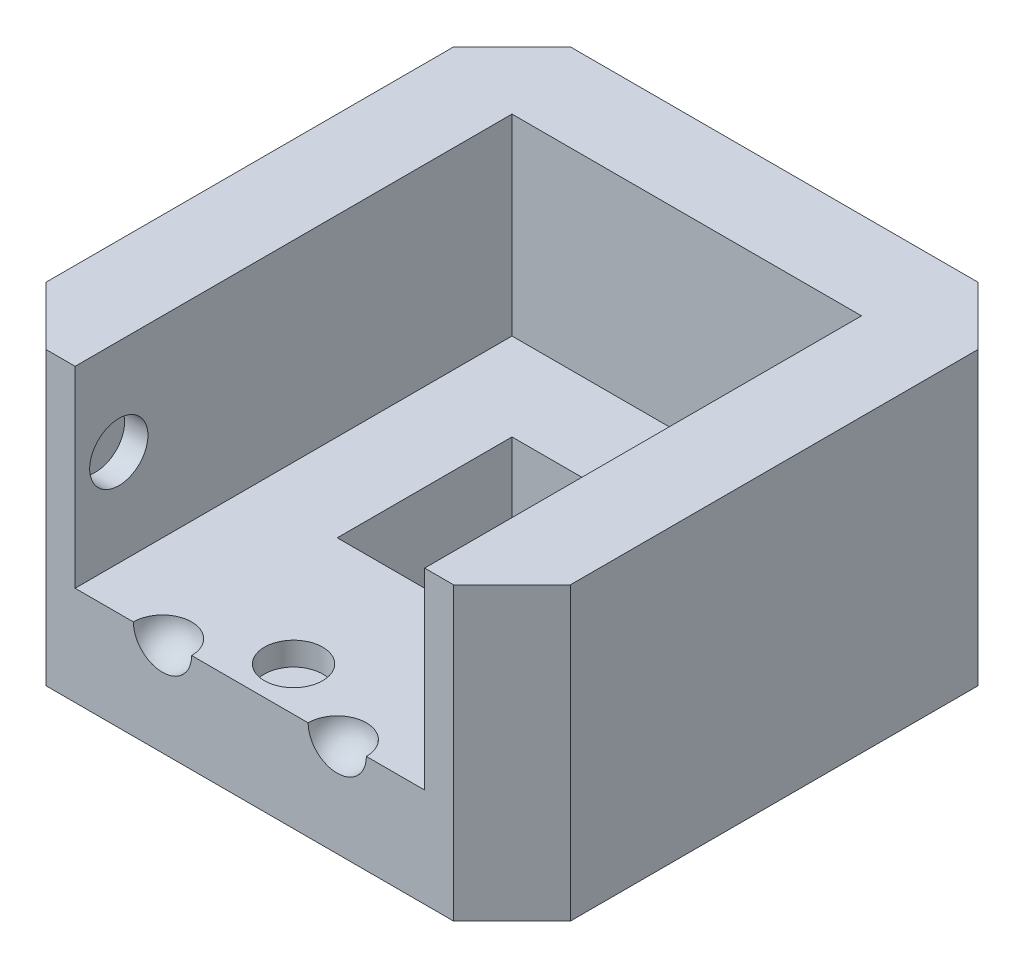
SolidWorks part; units mm, degrees
material "Polyurethane Foam Rigid"
ref_plane "Front Plane" through (0, 0, 0) normal (0, 0, 1) x (1, 0, 0)
ref_plane "Top Plane" through (0, 0, 0) normal (0, 1, 0) x (1, 0, 0)
ref_plane "Right Plane" through (0, 0, 0) normal (1, 0, 0) x (0, 0, -1)
sketch "Sketch1" plane through (0, 0, 0) normal (0, 1, 0) x (1, 0, 0)
  line L1 (-57.15, -57.15) -> (57.15, -57.15)
  line L2 (-57.15, -57.15) -> (-57.15, 57.15)
  line L3 (-57.15, 57.15) -> (57.15, 57.15)
  line L4 (57.15, -57.15) -> (57.15, 57.15)
  line L5 (-57.15, -57.15) -> (57.15, 57.15) construction
  line L6 (-57.15, 57.15) -> (57.15, -57.15) construction
  line L7 (-19.05, -19.05) -> (19.05, -19.05)
  line L8 (-19.05, -19.05) -> (-19.05, 19.05)
  line L9 (-19.05, 19.05) -> (19.05, 19.05)
  line L10 (19.05, -19.05) -> (19.05, 19.05)
  line L11 (-19.05, -19.05) -> (19.05, 19.05) construction
  line L12 (-19.05, 19.05) -> (19.05, -19.05) construction
  point P0 (0, 0)
  point P6 (0, 0)
  dimension "D1" = 114.3
  dimension "D2" = 114.3
  dimension "D3" = 38.1
  dimension "D4" = 38.1
extrude "Boss-Extrude1" add sketch "Sketch1" along normal blind 76.2
sketch "Sketch3" plane through (0, 76.2, 0) normal (0, 1, 0) x (1, 0, 0)
  line L1 (-38.1, -38.1) -> (38.1, -38.1)
  line L2 (-38.1, -38.1) -> (-38.1, 38.1)
  line L3 (-38.1, 38.1) -> (38.1, 38.1)
  line L4 (38.1, -38.1) -> (38.1, 38.1)
  line L5 (-38.1, -38.1) -> (38.1, 38.1) construction
  line L6 (-38.1, 38.1) -> (38.1, -38.1) construction
  point P0 (0, 0)
  dimension "D1" = 76.2
  dimension "D2" = 76.2
extrude "Cut-Extrude2" cut sketch "Sketch3" against normal blind 54.61
sketch "Sketch5" plane through (0, 76.2, 0) normal (0, 1, 0) x (1, 0, 0)
  line L1 (-38.1, -38.1) -> (38.1, -38.1)
  line L2 (-38.1, -38.1) -> (-38.1, 38.1)
  line L3 (-38.1, 38.1) -> (38.1, 38.1)
  line L4 (38.1, -38.1) -> (38.1, 38.1)
  line L5 (-38.1, -38.1) -> (38.1, 38.1) construction
  line L6 (-38.1, 38.1) -> (38.1, -38.1) construction
  line L7 (-57.15, -57.15) -> (57.15, -57.15)
  line L8 (-57.15, -57.15) -> (-57.15, 57.15)
  line L9 (-57.15, 57.15) -> (57.15, 57.15)
  line L10 (57.15, -57.15) -> (57.15, 57.15)
  line L11 (-57.15, -57.15) -> (57.15, 57.15) construction
  line L12 (-57.15, 57.15) -> (57.15, -57.15) construction
  point P0 (0, 0)
  point P7 (0, 0)
extrude "Cut-Extrude3" cut sketch "Sketch5" against normal blind 12.7
chamfer "Chamfer1" distance 12.7 angle 45 4 edges at (-57.15, 31.75, 57.15) (-57.15, 31.75, -57.15) (57.15, 31.75, -57.15) (57.15, 31.75, 57.15)
sketch "Sketch6" plane through (0, 0, 57.15) normal (0, 0, 1) x (1, 0, 0)
  line L0 (-44.45, 63.5) -> (44.45, 63.5) construction
  line L1 (-38.1, 63.5) -> (38.1, 63.5)
  line L2 (-38.1, 63.5) -> (-38.1, 21.59)
  line L3 (-38.1, 21.59) -> (38.1, 21.59)
  line L4 (38.1, 63.5) -> (38.1, 21.59)
  point P6 (0, 21.59)
  dimension "D1" = 41.91
  dimension "D2" = 76.2
extrude "Cut-Extrude4" cut sketch "Sketch6" against normal up to next
sketch "Sketch7" plane through (0, 21.59, 0) normal (0, 1, 0) x (1, 0, 0)
  line L0 (-57.15, -57.15) -> (57.15, -57.15) construction
  circle A0 centre (0, -47.625) radius 6.35
  dimension "D1" = 12.7
  dimension "D2" = 9.525
extrude "Cut-Extrude5" cut sketch "Sketch7" against normal blind 5.08
sketch "Sketch8" plane through (-38.1, 0, 0) normal (1, 0, 0) x (0, 0, -1)
  line L1 (-57.15, 63.5) -> (-57.15, 21.59) construction
  circle A0 centre (-47.625, 42.545) radius 6.35
  dimension "D1" = 12.7
  dimension "D2" = 9.525
sketch "Sketch9" plane through (38.1, 0, 0) normal (-1, 0, 0) x (0, 0, 1)
  circle A0 centre (47.625, 42.545) radius 6.35
  dimension "D1" = 12.7
extrude "Cut-Extrude6" cut sketch "Sketch9" against normal blind 5.08 contours A0
extrude "Cut-Extrude7" cut sketch "Sketch8" against normal blind 5.08 contours A0
sketch "Sketch10" plane through (0, 0, 57.15) normal (0, 0, 1) x (1, 0, 0)
  line L0 (-38.1, 21.59) -> (38.1, 21.59) construction
  line L1 (-25.4, 21.59) -> (-12.7, 21.59)
  line L2 (0, -34.925) -> (0, 34.925) construction
  line L3 (25.4, 21.59) -> (12.7, 21.59)
  arc A0 (-25.4, 21.59) -> (-12.7, 21.59) centre (-19.05, 21.59) ccw
  arc A1 (25.4, 21.59) -> (12.7, 21.59) centre (19.05, 21.59) cw
  dimension "D1" = 6.35
revolve "Cut-Revolve1" cut sketch "Sketch10" angle 360 about L1 region at (-19.05, 18.895, 57.15) region at (19.05, 18.895, 57.15)
